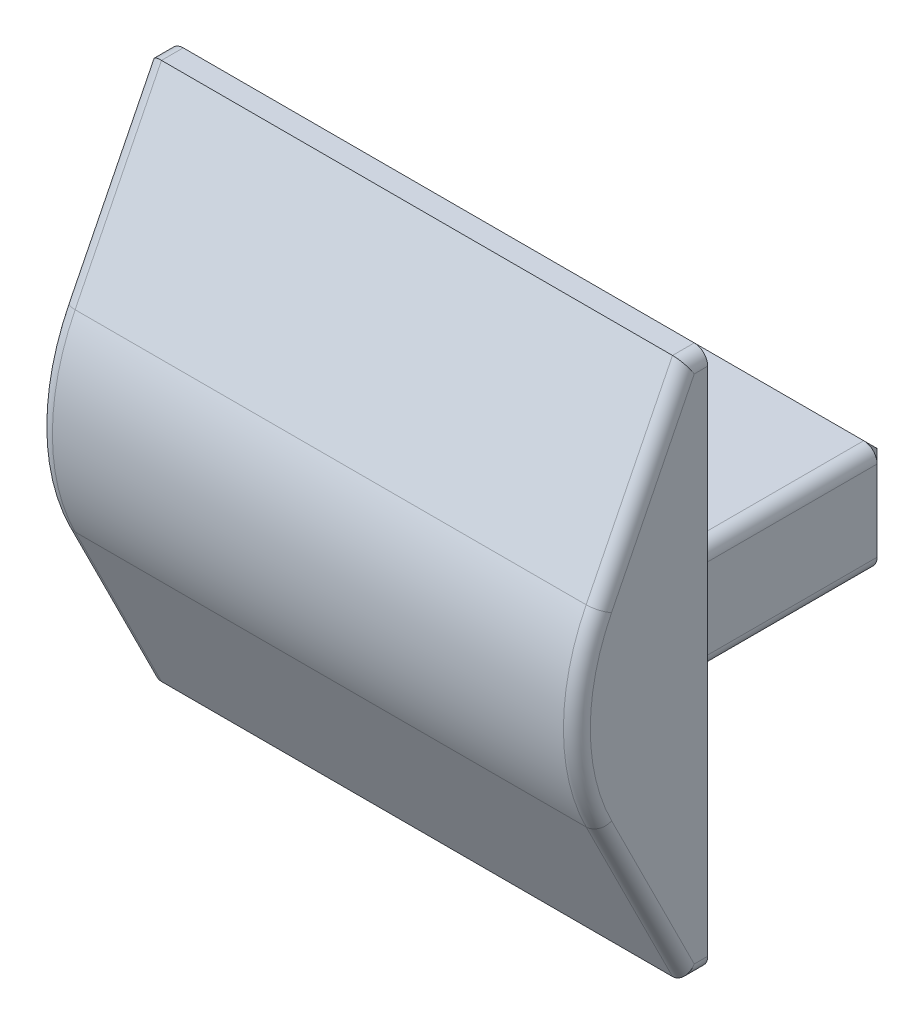
SolidWorks part; units mm, degrees
note: The reader was unsure of these and kept them because the rebuilt part matched: shared geometry of "Sketch3<4>".
ref_plane "Front Plane" through (0, 0, 0) normal (0, 0, 1) x (1, 0, 0)
ref_plane "Top Plane" through (0, 0, 0) normal (0, 1, 0) x (1, 0, 0)
ref_plane "Right Plane" through (0, 0, 0) normal (1, 0, 0) x (0, 0, -1)
ref_plane "Plane1" through (25.9401, 0, 0) normal (1, 0, 0) x (0, 0, -1)
sketch "Sketch3" plane through (25.9401, 0, 0) normal (1, 0, 0) x (0, 0, -1)
  line L0 (-28.7936, -877.6366) -> (-28.7936, -857.6366)
  line L1 (-42.1966, -867.6366) -> (-16.5369, -867.6366) construction
  line L2 (-29.6022, -877.6366) -> (-32.8134, -871.2143)
  line L3 (-29.6022, -857.6366) -> (-32.8134, -864.0589)
  line L4 (-28.7936, -869.6366) -> (-20.2936, -869.6366)
  line L5 (-20.2936, -869.6366) -> (-20.2936, -865.6366)
  line L6 (-28.7936, -865.6366) -> (-20.2936, -865.6366)
  line L8 (-26.4602, -877.6366) -> (-28.6936, -877.6366) construction
  line L9 (-29.7936, -877.9366) -> (-29.7936, -842.9366) construction
  line L12 (-29.7936, -877.9366) -> (-34.7936, -867.9366) construction
  line L13 (-20.2936, -854.4366) -> (-20.2936, -882.9366) construction
  line L14 (-28.7936, -877.6366) -> (-29.6022, -877.6366)
  line L15 (-28.7936, -857.6366) -> (-29.6022, -857.6366)
  arc A0 (-32.8134, -864.0589) -> (-32.8134, -871.2143) centre (-25.658, -867.6366) ccw
  point P9 (-20.2936, -867.6366)
  point P20 (-34.6022, -867.6366)
  dimension "D5" = 8
  dimension "D1" = 1
  dimension "D2" = 20
  dimension "D3" = 4
  dimension "D4" = 0.8087
extrude "Boss-Extrude1" add sketch "Sketch3" along normal offset from surface 0.5 and the other way offset from surface (10 mm away) 0.5 contours L3 L1 L0 | L1 L2 L0
extrude "Boss-Extrude2" add sketch "Sketch3<4>" along normal offset from surface 0.1 and the other way offset from surface (8.3 mm away) 0.1 contours L1 L0 L4 L5 | L0 L1 L5 L6
sketch "Sketch3<4>" plane through (25.9401, 0, 0) normal (1, 0, 0) x (0, 0, -1) same geometry as "Sketch3"
fillet "Fillet1" radius 0.5 14 edges at (17.6401, -869.6366, 24.5436) (17.6401, -865.6366, 24.5436) (34.2401, -869.6366, 24.5436) (34.2401, -865.6366, 24.5436) (35.9401, -860.8477, 31.2078) (35.9401, -874.4254, 31.2078) (15.9401, -874.4254, 31.2078) (15.9401, -867.6366, 33.658) (35.9401, -867.6366, 33.658) (15.9401, -860.8477, 31.2078) (15.9401, -857.6366, 29.1979) (15.9401, -877.6366, 29.1979) (35.9401, -877.6366, 29.1979) (35.9401, -857.6366, 29.1979)
chamfer "Chamfer1" distance 0.5 angle 45 8 edges at (34.2401, -867.6366, 20.2936) (34.0936, -865.783, 20.2936) (34.0936, -869.4901, 20.2936) (25.9401, -865.6366, 20.2936) (25.9401, -869.6366, 20.2936) (17.7865, -865.783, 20.2936) (17.7865, -869.4901, 20.2936) (17.6401, -867.6366, 20.2936)
